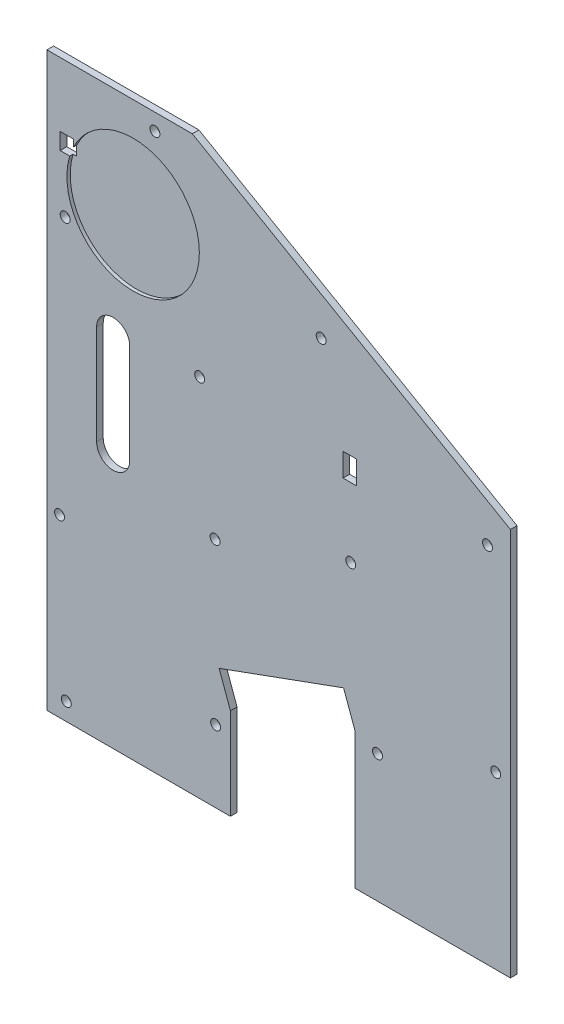
SolidWorks part; units mm, degrees
ref_plane "Front Plane" through (0, 0, 0) normal (0, 0, 1) x (1, 0, 0)
ref_plane "Top Plane" through (0, 0, 0) normal (0, 1, 0) x (1, 0, 0)
ref_plane "Right Plane" through (0, 0, 0) normal (1, 0, 0) x (0, 0, -1)
sketch "Sketch1" plane through (0, 0, 0) normal (0, 0, 1) x (1, 0, 0)
  line L19 (-70, 100) -> (-70, -72.7995) construction
  line L21 (70, -72.7995) -> (70, 44.5248) construction
  line L22 (-26.0859, 100) -> (70, 44.5248) construction
  line L23 (-26.0859, 100) -> (-70, 100) construction
  line L24 (-70, 100) -> (-70, -72.7995)
  line L25 (-70, -72.7995) -> (70, -72.7995)
  line L26 (70, -72.7995) -> (70, 44.5248)
  line L27 (-26.0859, 100) -> (70, 44.5248)
  line L28 (-26.0859, 100) -> (-70, 100)
extrude "Boss-Extrude1" add sketch "Sketch1" along normal blind 2
sketch "Sketch2" plane through (0, 0, 2) normal (0, 0, 1) x (1, 0, 0)
  line L5 (-26.0859, 100) -> (-70, 100)
  line L6 (-70, 100) -> (-70, -72.7995)
  line L7 (-70, -72.7995) -> (70, -72.7995)
  line L8 (70, -72.7995) -> (70, 44.5248)
  line L9 (70, 44.5248) -> (-26.0859, 100)
  line L10 (-26.0859, 100) -> (-70, 100)
  line L11 (-70, 100) -> (-70, -72.7995)
  line L12 (-70, -72.7995) -> (70, -72.7995)
  line L13 (70, -72.7995) -> (70, 44.5248)
  line L14 (70, 44.5248) -> (-26.0859, 100)
  circle A0 centre (-43.9688, 69.9102) radius 20
  dimension "D1" = 0
sketch "Sketch3" plane through (0, 0, 2) normal (0, 0, 1) x (1, 0, 0)
  line L0 (-17.9925, -35.7876) -> (19.5952, -22.1068)
  line L2 (19.5952, -22.1068) -> (23.0154, -31.5037)
  line L4 (-70, -65.3585) -> (-14.5723, -45.1845) construction
  line L5 (-66, 75.6554) -> (-62, 75.6554) construction
  line L6 (-66, 75.6554) -> (-62, 75.6554)
  line L7 (-66, 80.6554) -> (-66, 75.6554) construction
  line L8 (-66, 80.6554) -> (-62, 80.6554) construction
  line L9 (-62, 80.6554) -> (-62, 75.6554) construction
  line L10 (-26.0859, 100) -> (-70, 100)
  line L11 (-70, 100) -> (-70, -72.7995)
  line L12 (-70, -72.7995) -> (70, -72.7995)
  line L13 (70, -72.7995) -> (70, 44.5248)
  line L14 (70, 44.5248) -> (-26.0859, 100)
  line L15 (-26.0859, 100) -> (-70, 100)
  line L16 (-70, 100) -> (-70, -72.7995)
  line L17 (-70, -72.7995) -> (70, -72.7995)
  line L18 (70, -72.7995) -> (70, 44.5248)
  line L19 (70, 44.5248) -> (-26.0859, 100)
  line L20 (-66, 80.6554) -> (-66, 75.6554)
  line L21 (-66, 80.6554) -> (-62, 80.6554)
  line L22 (-62, 80.6554) -> (-62, 75.6554)
  line L23 (19.4272, 32.69) -> (23.4317, 32.69) construction
  line L24 (19.4272, 32.69) -> (19.4272, 39.6978) construction
  line L25 (23.4317, 32.69) -> (23.4317, 39.6978) construction
  line L26 (19.4272, 39.6978) -> (23.4317, 39.6978) construction
  line L27 (19.4272, 32.69) -> (23.4317, 32.69)
  line L28 (19.4272, 32.69) -> (19.4272, 39.6978)
  line L29 (23.4317, 32.69) -> (23.4317, 39.6978)
  line L30 (19.4272, 39.6978) -> (23.4317, 39.6978)
  line L31 (-17.9925, -35.7876) -> (-14.5723, -45.1845)
  line L32 (-14.5723, -45.1845) -> (-14.5723, -75.1845)
  line L33 (-14.5723, -75.1845) -> (23.0154, -75.1845)
  line L34 (23.0154, -75.1845) -> (23.0154, -31.5037)
  dimension "D1" = 10
  dimension "D2" = 30
  dimension "D3" = 0
extrude "Cut-Extrude1" cut sketch "Sketch3" against normal blind 10 contours L30 L28 L27 L29 | L22 L21 L20 L6 | L33 L34 L2 L0 L31 L32 | L0 L2 L34 L33 L32 L31 region at (4.7682, -50.2249, 2) region at (-64, 78.1554, 2) region at (21.4295, 36.1939, 2)
sketch "Sketch4" plane through (0, 0, 2) normal (0, 0, 1) x (1, 0, 0)
  circle A0 centre (-43.9688, 69.9102) radius 20 construction
  circle A1 centre (-43.9688, 69.9102) radius 20
extrude "Cut-Extrude2" cut sketch "Sketch4" against normal blind 1
hole_wizard "Ø3.0mm Press Dowel Hole1" positions "Sketch5" profile "Sketch6" hole size "Ø3.0" standard "ANSI Metric"
sketch "Sketch5" plane through (-89.742, -119.4997, 0) normal (0, 0, -1) x (-1, 0, 0)
  point P0 (-23.5423, 99.781)
  point P1 (-25.5944, 52.0145)
  point P2 (-70.6996, 68.4315)
  point P3 (-70.5269, 116.8821)
  point P4 (-111.4918, 131.26)
  point P5 (-119.5864, 85.3143)
  point P6 (-155.2948, 98.311)
  point P7 (-152.8064, 156.4818)
  point P8 (-65.8782, 157.0177)
  point P9 (-102.577, 185.4818)
  point P10 (-52.3475, 214.4818)
  point P11 (-25.242, 178.4997)
  point P24 (0, 0)
sketch "Sketch6" plane through (-66.1998, -19.7187, 0) normal (1, 0, 0) x (0, 1, 0)
  line L0 (0, 0) -> (0, 1.999)
  line L1 (0, 1.999) -> (1.5, 1.999)
  line L2 (1.5, 1.999) -> (1.5, 0)
  line L3 (1.5, 0) -> (0, 0)
  line L4 (0, -6.35) -> (0, 107.95) construction
  dimension "Thru Hole Dia." = 3
  dimension "Thru Hole Depth" = 1.999
extrude "Cut-Extrude3" cut sketch "Sketch7" against normal through all
sketch "Sketch7" plane through (-89.742, -119.4997, 2) normal (0, 0, 1) x (1, 0, 0)
  line L0 (39.742, 154.4997) -> (39.742, 124.4997) construction
  line L1 (44.742, 154.4997) -> (44.742, 124.4997)
  line L2 (34.742, 154.4997) -> (34.742, 124.4997)
  arc A0 (44.742, 154.4997) -> (34.742, 154.4997) centre (39.742, 154.4997) ccw
  arc A1 (34.742, 124.4997) -> (44.742, 124.4997) centre (39.742, 124.4997) ccw
  point P2 (39.742, 139.4997)
  point P9 (0, 0)
